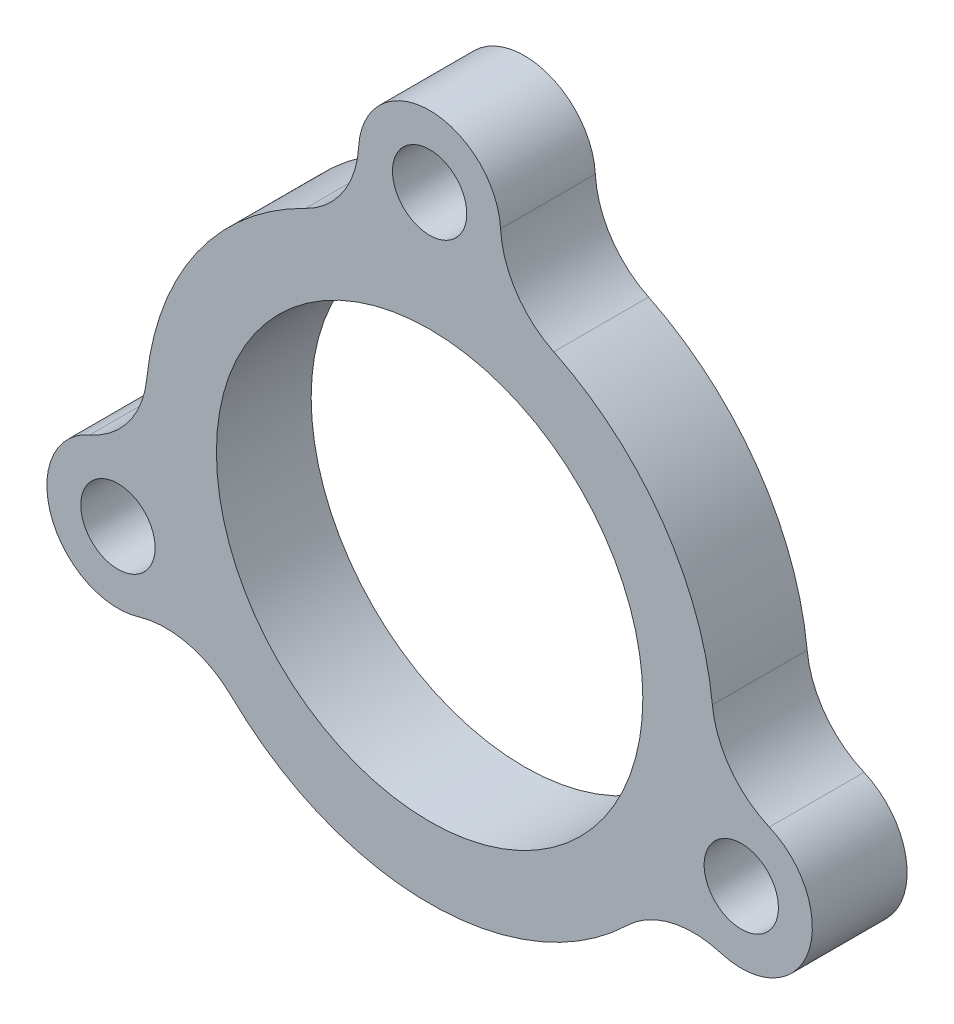
SolidWorks part; units mm, degrees
material "6061-T6 (SS)"
ref_plane "Front Plane" through (0, 0, 0) normal (0, 0, 1) x (1, 0, 0)
ref_plane "Top Plane" through (0, 0, 0) normal (0, 1, 0) x (1, 0, 0)
ref_plane "Right Plane" through (0, 0, 0) normal (1, 0, 0) x (0, 0, -1)
sketch "Sketch2" plane through (0, 0, 0) normal (0, 0, 1) x (1, 0, 0)
  line L0 (0, 0) -> (-20.8847, -7.6014) construction
  line L3 (0, 0) -> (20.8847, -7.6014) construction
  line L4 (0, 0) -> (0, 22.225) construction
  circle A0 centre (0, 0) radius 14.2875
  circle A1 centre (0, 22.225) radius 2.4892
  circle A2 centre (20.8847, -7.6014) radius 2.4892
  circle A3 centre (-20.8847, -7.6014) radius 2.4892
  circle A4 centre (20.8847, -7.6014) radius 4.7625
  circle A5 centre (0, 0) radius 19.05
  circle A6 centre (0, 22.225) radius 4.7625
  circle A7 centre (-20.8847, -7.6014) radius 4.7625
  point P11 (0, 0)
  point P13 (-20.5931, -8.3591)
  dimension "D1" = 28.575
  dimension "D2" = 4.9784
  dimension "D6" = 9.525
  dimension "D5" = 38.1
  dimension "D3" = 22.225
  dimension "D4" = 110
  dimension "D7" = 110
extrude "Boss-Extrude1" add sketch "Sketch2" along normal blind 6.35 contours A7 A5 A4 A6 A0 | A5 A6 A1 | A5 A4 A2 | A5 A7 A3 | A5 A6 | A4 A5 | A5 A7 region at (21.825, -12.1355, 0) region at (17.2435, -6.2761, 0) region at (15.9049, -5.7889, 0) region at (-25.236, -9.1851, 0) region at (-17.2435, -6.2761, 0) region at (0, 18.3501, 0) region at (0, 19.1758, 0)
fillet "Fillet2" radius 6.35 6 edges at (-18.7546, -3.3418, 3.175) (-3.2742, 18.7665, 3.175) (18.7546, -3.3418, 3.175) (16.5149, -9.4953, 3.175) (-16.5149, -9.4953, 3.175) (3.2742, 18.7665, 3.175)
equation "\"D7@Sketch2\"=\"D4@Sketch2\""
